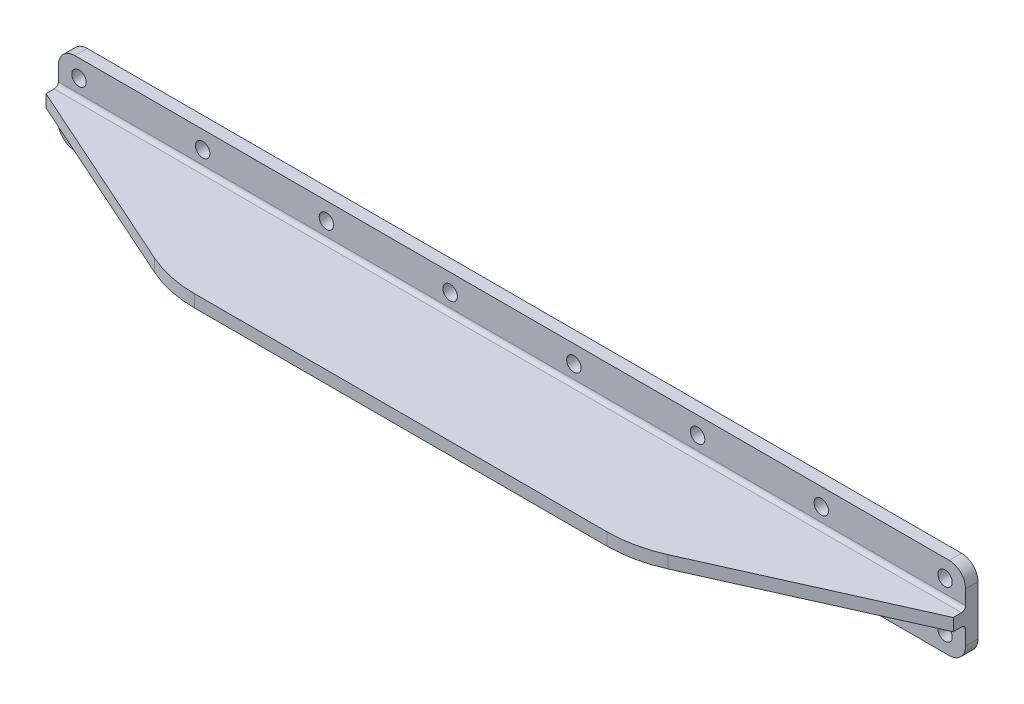
SolidWorks part; units mm, degrees
ref_plane "Top Plane" through (0, 0, 0) normal (0, 0, 1) x (1, 0, 0)
ref_plane "Right Plane" through (0, 0, 0) normal (0, 1, 0) x (1, 0, 0)
ref_plane "Front Plane" through (0, 0, 0) normal (1, 0, 0) x (0, 0, -1)
sketch "Sketch1" plane through (0, 0, 0) normal (1, 0, 0) x (0, 0, -1)
  line L0 (-33, 0) -> (0, 0) construction
  line L1 (-33, -1.5) -> (-33, 1.5)
  line L2 (-33, 1.5) -> (-3, 1.5)
  line L3 (-3, 1.5) -> (-3, 10)
  line L4 (-3, 10) -> (0, 10)
  line L5 (0, 10) -> (0, -10)
  line L6 (-3, -10) -> (0, -10)
  line L7 (-3, -1.5) -> (-3, -10)
  line L8 (-33, -1.5) -> (-3, -1.5)
  dimension "D1" = 3
  dimension "D2" = 3
  dimension "D3" = 20
  dimension "D4" = 30
extrude "Boss-Extrude1" add sketch "Sketch1" along normal mid plane 220
sketch "Sketch2" plane through (0, 0, 3) normal (0, 0, 1) x (1, 0, 0)
  line L0 (0, 18.0483) -> (0, -17.5272) construction
  line L1 (-15, -1.5) -> (-15, -10) construction
  line L4 (110, -10) -> (-110, -10) construction
  line L5 (110, -1.5) -> (-110, -1.5) construction
  line L6 (-45, -5.75) -> (-15, -5.75) construction
  line L7 (45, -5.75) -> (15, -5.75) construction
  line L8 (15, -1.5) -> (15, -10) construction
  line L9 (15, -5.75) -> (-15, -5.75) construction
  line L10 (-102.4934, 0) -> (112.014, 0) construction
  line L11 (15, 5.75) -> (-15, 5.75) construction
  line L12 (15, 1.5) -> (15, 10) construction
  line L13 (45, 5.75) -> (15, 5.75) construction
  line L14 (-45, 5.75) -> (-15, 5.75) construction
  line L15 (-15, 1.5) -> (-15, 10) construction
  circle A0 centre (-15, -5.75) radius 1.75
  circle A1 centre (-15, -5.75) radius 3 construction
  circle A2 centre (-45, -5.75) radius 1.75
  circle A3 centre (-45, -5.75) radius 3 construction
  circle A4 centre (-75, -5.75) radius 1.75
  circle A5 centre (-75, -5.75) radius 3 construction
  circle A6 centre (-105, -5.75) radius 1.75
  circle A7 centre (-105, -5.75) radius 3 construction
  circle A11 centre (105, -5.75) radius 3 construction
  circle A12 centre (75, -5.75) radius 3 construction
  circle A13 centre (45, -5.75) radius 3 construction
  circle A14 centre (15, -5.75) radius 3 construction
  circle A16 centre (105, -5.75) radius 1.75
  circle A17 centre (75, -5.75) radius 1.75
  circle A18 centre (45, -5.75) radius 1.75
  circle A19 centre (15, -5.75) radius 1.75
  circle A20 centre (15, 5.75) radius 3 construction
  circle A21 centre (45, 5.75) radius 3 construction
  circle A22 centre (75, 5.75) radius 3 construction
  circle A23 centre (105, 5.75) radius 3 construction
  circle A26 centre (-105, 5.75) radius 3 construction
  circle A27 centre (-75, 5.75) radius 3 construction
  circle A28 centre (-45, 5.75) radius 3 construction
  circle A29 centre (-15, 5.75) radius 3 construction
  circle A30 centre (15, 5.75) radius 1.75
  circle A31 centre (45, 5.75) radius 1.75
  circle A32 centre (75, 5.75) radius 1.75
  circle A33 centre (105, 5.75) radius 1.75
  circle A36 centre (-105, 5.75) radius 1.75
  circle A37 centre (-75, 5.75) radius 1.75
  circle A38 centre (-45, 5.75) radius 1.75
  circle A39 centre (-15, 5.75) radius 1.75
  dimension "D1" = 6
  dimension "D2" = 3.5
  dimension "D4" = 30
  dimension "D3" = 4
extrude "Cut-Extrude1" cut sketch "Sketch2" against normal through all
sketch "Sketch3" plane through (0, 1.5, 0) normal (0, 1, 0) x (1, 0, 0)
  line L0 (-117.7645, 0) -> (120.942, 0) construction
  line L4 (62.262, -27.3796) -> (110, -6)
  line L5 (110, -3) -> (110, -33) construction
  line L6 (-62.262, -27.3796) -> (-110, -6)
  line L7 (-110, -3) -> (-110, -33) construction
  line L9 (-50, -30) -> (50, -30)
  line L12 (-110, -3) -> (-110, -33)
  line L13 (-110, -33) -> (110, -33)
  line L14 (110, -33) -> (110, -3)
  line L15 (110, -3) -> (-110, -3)
  line L16 (-110, -6) -> (-110, -33)
  line L17 (-110, -33) -> (110, -33)
  line L18 (110, -33) -> (110, -6)
  arc A1 (50, -30) -> (62.262, -27.3796) centre (50, 0) ccw
  arc A2 (-62.262, -27.3796) -> (-50, -30) centre (-50, 0) ccw
  point P5 (0, 0)
  point P6 (-44.8048, -29.9997)
  point P8 (40.9302, -28.5961)
  point P19 (0, 0)
  dimension "D2" = 6
  dimension "D1" = 6
  dimension "D3" = 30
  dimension "D5" = 60
  dimension "D6" = 60
  dimension "D7" = 60
  dimension "D4" = 0
extrude "Cut-Extrude2" cut sketch "Sketch3" against normal through all
fillet "Fillet1" radius 4 4 edges at (110, 10, 1.5) (110, -10, 1.5) (-110, -10, 1.5) (-110, 10, 1.5)
fillet "Fillet2" radius 1 2 edges at (0, -1.5, 3) (0, 1.5, 3)
